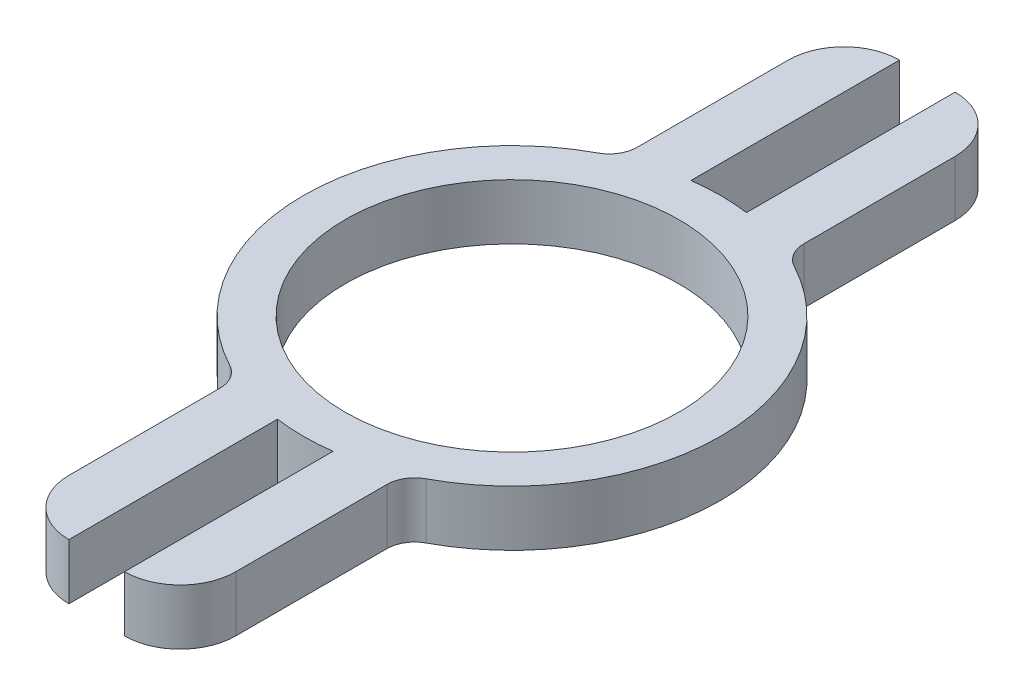
SolidWorks part; units mm, degrees
material "PTFE (general)"
ref_plane "Front Plane" through (0, 0, 0) normal (0, 0, 1) x (1, 0, 0)
ref_plane "Top Plane" through (0, 0, 0) normal (0, 1, 0) x (1, 0, 0)
ref_plane "Right Plane" through (0, 0, 0) normal (1, 0, 0) x (0, 0, -1)
sketch "Sketch1" plane through (0, 0, 0) normal (0, 1, 0) x (1, 0, 0)
  circle A0 centre (0, 0) radius 50
  circle A1 centre (0, 0) radius 75
  dimension "D1" = 100
  dimension "D2" = 150
extrude "Boss-Extrude1" add sketch "Sketch1" along normal blind 20
sketch "Sketch2" plane through (0, 0, 0) normal (0, 0, 1) x (1, 0, 0)
  line L1 (60, 1) -> (75, 1)
  line L2 (60, 1) -> (60, 20)
  line L3 (60, 20) -> (75, 20)
  line L4 (75, 1) -> (75, 20)
  line L5 (75, 20) -> (-75, 20) construction
  line L7 (-75, 0) -> (75, 0) construction
  line L8 (75, 0) -> (75, 20) construction
  dimension "D1" = 15
  dimension "D3" = 1
ref_axis "Axis1" through (0, 20, 0) along (0, -1, 0)
revolve "Cut-Revolve1" cut sketch "Sketch2" angle 360 about axis through (0, 20, 0) along (0, -1, 0) other way angle 360
sketch "Sketch4" plane through (0, 0, 0) normal (0, -1, 0) x (1, 0, 0)
  circle A0 centre (0, 0) radius 50 construction
  circle A1 centre (0, 0) radius 75
  circle A2 centre (0, 0) radius 75
  circle A3 centre (0, 0) radius 50
  dimension "D1" = 0
extrude "Boss-Extrude2" add sketch "Sketch4" along normal blind 20
sketch "Sketch5" plane through (0, 0, 0) normal (0, 1, 0) x (1, 0, 0)
  line L0 (0, -113.9207) -> (0, 276.226) construction
  line L3 (10, 74.3303) -> (10, 149.3303)
  line L4 (10, 149.3303) -> (30, 149.3303)
  line L5 (30, 149.3303) -> (30, 68.7386)
  circle A0 centre (0, 0) radius 75 construction
  arc A1 (30, 68.7386) -> (10, 74.3303) centre (0, 0) ccw
  point P12 (30, 68.7386)
  point P13 (10, 74.3303)
  dimension "D1" = 10
  dimension "D2" = 20
  dimension "D3" = 75
extrude "Boss-Extrude3" add sketch "Sketch5" against normal blind 20
mirror "Mirror1" about plane through (0, 0, 0) normal (1, 0, 0) of "Boss-Extrude3"
mirror "Mirror2" about plane through (0, 0, 0) normal (0, 0, 1) of "Boss-Extrude3", "Mirror1"
sketch "Sketch6" plane through (0, 20, 0) normal (0, 1, 0) x (1, 0, 0)
  circle A0 centre (0, 0) radius 50 construction
  circle A1 centre (0, 0) radius 60
  circle A2 centre (0, 0) radius 60
  circle A3 centre (0, 0) radius 50
  circle A4 centre (0, 0) radius 62
  circle M4 centre (0, 0) radius 50
  circle M5 centre (0, 0) radius 60
  dimension "D1" = 0
extrude "Boss-Extrude4" add sketch "Sketch6" along normal blind 8 contours M5 M4 region at (-58.3029, 20, 0)
fillet "Fillet1" radius 20 1 edges at (30, -10, -149.3303) type face fillet first side face at (30, -10, -109.0345) second side face at (20, -10, -149.3303)
fillet "Fillet2" radius 20 1 edges at (-30, -10, -149.3303) type face fillet first side face at (-30, -10, -109.0345) second side face at (-20, -10, -149.3303)
fillet "Fillet3" radius 20 1 edges at (-30, -10, 149.3303) type face fillet first side face at (-30, -10, 109.0345) second side face at (-20, -10, 149.3303)
fillet "Fillet4" radius 20 1 edges at (30, -10, 149.3303) type face fillet first side face at (30, -10, 109.0345) second side face at (20, -10, 149.3303)
sketch "Sketch7" plane through (0, 0, 0) normal (0, 1, 0) x (1, 0, 0)
  circle A0 centre (0, 0) radius 60 construction
  circle A1 centre (0, 0) radius 60
extrude "Cut-Extrude3" cut sketch "Sketch7" against normal through all both and the other way through all contours A1
sketch "Sketch9" plane through (0, 1, 0) normal (0, 1, 0) x (1, 0, 0)
  circle A0 centre (90.9537, -86.329) radius 265.669
extrude "Cut-Extrude4" cut sketch "Sketch9" against normal blind 1
fillet "Fillet5" radius 10 1 edges at (-30, -10, -68.7386) type face fillet first side face at (-52.5, -10, 0) second side face at (-30, -10, -99.0345)
fillet "Fillet6" radius 10 1 edges at (30, -10, -68.7386) type face fillet first side face at (52.5, -10, 0) second side face at (30, -10, -99.0345)
fillet "Fillet7" radius 10 1 edges at (30, -10, 68.7386) type face fillet first side face at (53.7947, -10, 2.1109) second side face at (30, -10, 99.0345)
fillet "Fillet8" radius 10 1 edges at (-30, -10, 68.7386) type face fillet first side face at (-30, -10, 99.0345) second side face at (-53.7947, -10, 2.1109)
